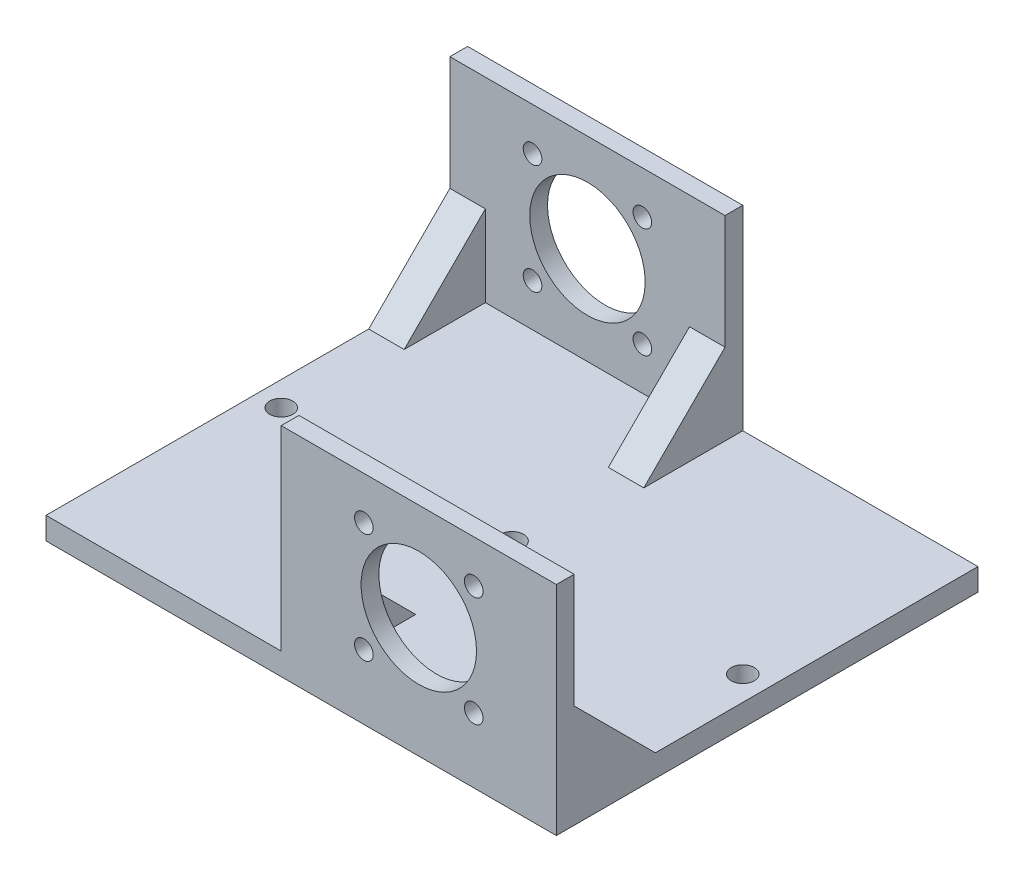
SolidWorks part; units mm, degrees
other "Markup1"
sketch "Sketch10" plane through (-57.5, 49, -37.5) normal (0, 1, 0) x (1, 0, 0)
material "ABS"
ref_plane "Front Plane" through (0, 0, 0) normal (0, 0, 1) x (1, 0, 0)
ref_plane "Top Plane" through (0, 0, 0) normal (0, 1, 0) x (1, 0, 0)
ref_plane "Right Plane" through (0, 0, 0) normal (1, 0, 0) x (0, 0, -1)
sketch "Sketch2" plane through (0, 0, 0) normal (0, 1, 0) x (1, 0, 0)
  line L1 (-57.5, 47.5) -> (57.5, 47.5)
  line L2 (-57.5, 47.5) -> (-57.5, -47.5)
  line L3 (-57.5, -47.5) -> (57.5, -47.5)
  line L4 (57.5, 47.5) -> (57.5, -47.5)
  line L5 (-57.5, 47.5) -> (57.5, -47.5) construction
  line L6 (-57.5, -47.5) -> (57.5, 47.5) construction
  point P0 (0, 0)
  dimension "D1" = 115
  dimension "D2" = 95
extrude "Boss-Extrude1" add sketch "Sketch2" along normal blind 5
sketch "Sketch3" plane through (0, 5, 0) normal (0, 1, 0) x (1, 0, 0)
  line L1 (-57.5, 47.5) -> (4.5, 47.5)
  line L2 (-57.5, 47.5) -> (-57.5, 43.5)
  line L3 (-57.5, 43.5) -> (4.5, 43.5)
  line L4 (4.5, 47.5) -> (4.5, 43.5)
  line L5 (57.5, -47.5) -> (-4.5, -47.5)
  line L6 (57.5, -47.5) -> (57.5, -43.5)
  line L7 (57.5, -43.5) -> (-4.5, -43.5)
  line L8 (-4.5, -47.5) -> (-4.5, -43.5)
  dimension "D1" = 62
  dimension "D2" = 4
  dimension "D3" = 62
  dimension "D4" = 4
extrude "Boss-Extrude2" add sketch "Sketch3" along normal blind 44
sketch "Sketch5" plane through (57.5, 0, 0) normal (1, 0, 0) x (0, 0, -1)
  line L0 (-43.5, 23.3068) -> (-25.1932, 5)
  line L1 (-43.5, 49) -> (-43.5, 5) construction
  line L2 (-43.5, 5) -> (47.5, 5) construction
  dimension "D1" = 45
  dimension "D2" = 25.8898
rib "Rib1" sketch "Sketch5" sketch "Sketch5" thickness 8 extrusion direction parallel to sketch draft on no parameters "D1"=8
sketch "Sketch6" plane through (-4.5, 0, 0) normal (-1, 0, 0) x (0, 0, 1)
  line L0 (25.1932, 5) -> (43.5, 23.3068)
rib "Rib2" sketch "Sketch6" sketch "Sketch6" thickness 8 extrusion direction parallel to sketch draft on no parameters "D1"=8
sketch "Sketch7" plane through (-57.5, 0, 0) normal (-1, 0, 0) x (0, 0, 1)
  line L0 (-43.5, 23.2999) -> (-25.2001, 5)
  line L3 (-43.5, 49) -> (-43.5, 5) construction
  line L4 (-43.5, 5) -> (47.5, 5) construction
  dimension "D1" = 25.88
  dimension "D2" = 45
rib "Rib6" sketch "Sketch7" sketch "Sketch7" thickness 8 extrusion direction parallel to sketch draft on no parameters "D1"=8
sketch "Sketch9" plane through (4.5, 0, 0) normal (1, 0, 0) x (0, 0, -1)
  line L0 (43.5, 23.2999) -> (25.2001, 5)
  line L1 (25.2001, 5) -> (43.5, 5)
  line L2 (43.5, 5) -> (43.5, 23.2999)
extrude "Boss-Extrude3" add sketch "Sketch9" against normal blind 8
sketch "Sketch11" plane through (0, 0, -47.5) normal (0, 0, -1) x (-1, 0, 0)
  circle A0 centre (26.5, 27) radius 13
  circle A1 centre (26.5, 27) radius 17.5 construction
  circle A3 centre (38.8744, 39.3744) radius 2.1
  circle A5 centre (38.8744, 14.6256) radius 2.1
  circle A7 centre (14.1256, 14.6256) radius 2.1
  circle A9 centre (14.1256, 39.3744) radius 2.1
  point P22 (26.5, 27)
extrude "Cut-Extrude1" cut sketch "Sketch11" against normal blind 4
sketch "Sketch12" plane through (0, 0, 47.5) normal (0, 0, 1) x (1, 0, 0)
  circle A0 centre (26.5, 27) radius 13
  circle A1 centre (26.5, 27) radius 17.5 construction
  circle A3 centre (38.8744, 39.3744) radius 2.1
  circle A5 centre (38.8744, 14.6256) radius 2.1
  circle A7 centre (14.1256, 14.6256) radius 2.1
  circle A9 centre (14.1256, 39.3744) radius 2.1
  point P22 (26.5, 27)
extrude "Cut-Extrude2" cut sketch "Sketch12" against normal blind 4
sketch "Sketch13" plane through (0, 5, 0) normal (0, 1, 0) x (1, 0, 0)
  line L0 (0, 0) -> (0, -10.7167) construction
  circle A0 centre (0, 0) radius 2.6
  circle A1 centre (52, 0) radius 2.6
  circle A3 centre (-52, 0) radius 2.6
  dimension "D1" = 52
extrude "Cut-Extrude3" cut sketch "Sketch13" against normal blind 5
